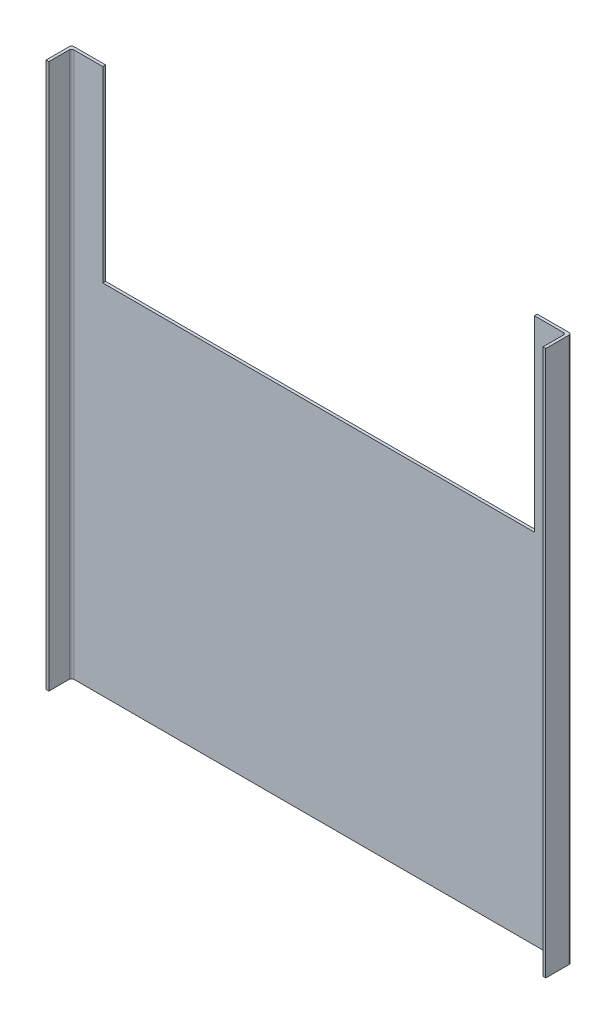
SolidWorks part; units mm, degrees
ref_plane "Front Plane" through (0, 0, 0) normal (0, 0, 1) x (1, 0, 0)
ref_plane "Top Plane" through (0, 0, 0) normal (0, 1, 0) x (1, 0, 0)
ref_plane "Right Plane" through (0, 0, 0) normal (1, 0, 0) x (0, 0, -1)
sketch "Sketch1" plane through (0, 0, 0) normal (0, 0, 1) x (1, 0, 0)
  line L0 (1041.4, 1219.2) -> (1117.6, 1219.2)
  line L1 (0, 0) -> (1117.6, 0)
  line L2 (0, 0) -> (0, 1219.2)
  line L3 (0, 1219.2) -> (76.2, 1219.2)
  line L4 (1117.6, 0) -> (1117.6, 1219.2)
  line L6 (76.2, 1219.2) -> (76.2, 800)
  line L7 (76.2, 800) -> (1041.4, 800)
  line L8 (1041.4, 1219.2) -> (1041.4, 800)
  dimension "D1" = 1117.6
  dimension "D2" = 1219.2
  dimension "D3" = 76.2
  dimension "D4" = 76.2
  dimension "D5" = 419.2
extrude "Boss-Extrude1" add sketch "Sketch1" along normal blind 6.35 contours L3 L6 L7 L8 L0 L4 L1 L2
sketch "Sketch2" plane through (0, 0, 6.35) normal (0, 0, 1) x (1, 0, 0)
  line L0 (0, 0) -> (1117.6, 0) construction
  line L1 (0, 1219.2) -> (6.35, 1219.2)
  line L2 (0, 1219.2) -> (0, 0)
  line L3 (0, 0) -> (6.35, 0)
  line L4 (6.35, 1219.2) -> (6.35, 0)
  line L6 (1117.6, 1219.2) -> (1111.25, 1219.2)
  line L7 (1117.6, 1219.2) -> (1117.6, 0)
  line L8 (1117.6, 0) -> (1111.25, 0)
  line L9 (1111.25, 1219.2) -> (1111.25, 0)
  dimension "D1" = 6.35
extrude "Boss-Extrude2" add sketch "Sketch2" along normal blind 50.8
fillet "Fillet1" radius 5 4 edges at (1117.6, 609.6, 0) (0, 609.6, 0) (1111.25, 609.6, 6.35) (6.35, 609.6, 6.35)
sketch "Sketch3" plane through (0, 0, 0) normal (0, 0, -1) x (-1, 0, 0)
  line L0 (-558.8, 800) -> (-558.8, 0) construction
  line L1 (-76.2, 800) -> (-1041.4, 800) construction
  line L2 (-5, 0) -> (-1112.6, 0) construction
  line L4 (-708.8, 250) -> (-408.8, 250)
  line L5 (-708.8, 250) -> (-708.8, 550)
  line L6 (-708.8, 550) -> (-408.8, 550)
  line L7 (-408.8, 250) -> (-408.8, 550)
  line L8 (-708.8, 250) -> (-408.8, 550) construction
  line L9 (-708.8, 550) -> (-408.8, 250) construction
  point P6 (-558.8, 400)
  dimension "D1" = 300
  dimension "D2" = 300
extrude "Cut-Extrude1" [suppressed] cut sketch "Sketch3" against normal through all
